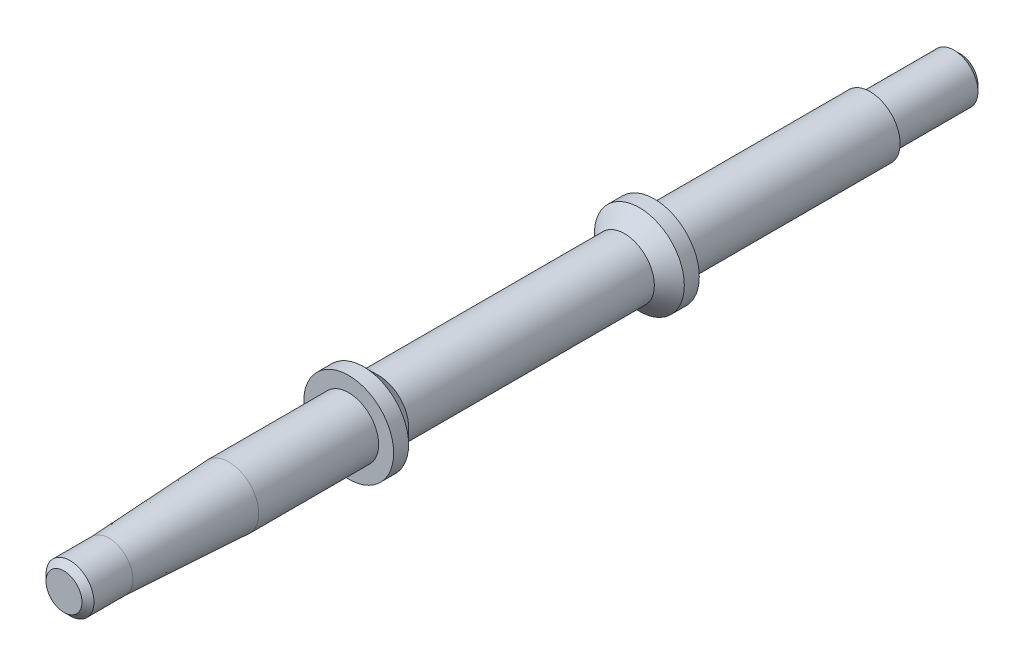
SolidWorks part; units mm, degrees
material "Ст20"
ref_plane "Front Plane" through (0, 0, 0) normal (0, 0, 1) x (1, 0, 0)
ref_plane "Top Plane" through (0, 0, 0) normal (0, 1, 0) x (1, 0, 0)
ref_plane "Right Plane" through (0, 0, 0) normal (1, 0, 0) x (0, 0, -1)
sketch "Эскиз1" plane through (0, 0, 0) normal (0, 0, 1) x (1, 0, 0)
  circle A0 centre (0, 0) radius 7.5
extrude "Бобышка-Вытянуть1" add sketch "Эскиз1" against normal blind 51
sketch "Эскиз2" plane through (0, 0, 0) normal (0, 0, 1) x (1, 0, 0)
  circle A0 centre (0, 0) radius 5
extrude "Бобышка-Вытянуть2" add sketch "Эскиз2" along normal blind 20
sketch "Эскиз3" plane through (0, 0, -51) normal (0, 0, -1) x (-1, 0, 0)
  circle A0 centre (0, 0) radius 5
extrude "Бобышка-Вытянуть3" add sketch "Эскиз3" along normal blind 36
cosmetic thread "Условное изображение резьбы1" parameters "D1"=19, "D2"=8.344
ref_plane "Плоскость1" through (0, 0, -2.5) normal (0, 0, 1) x (1, 0, 0)
sketch "Эскиз4" plane through (0, 0, -2.5) normal (0, 0, 1) x (1, 0, 0)
  circle A0 centre (0, 0) radius 5
extrude "Вырез-Вытянуть1" cut sketch "Эскиз4" against normal blind 46 flip side to cut
sketch "Эскиз5" plane through (0, 0, -87) normal (0, 0, -1) x (-1, 0, 0)
  circle A0 centre (0, 0) radius 4
extrude "Бобышка-Вытянуть4" add sketch "Эскиз5" along normal blind 15
sketch "Эскиз6" plane through (0, 0, 20) normal (0, 0, 1) x (1, 0, 0)
  circle A0 centre (0, 0) radius 5
extrude "Бобышка-Вытянуть5" add sketch "Эскиз6" along normal blind 20 draft 2.863
sketch "Эскиз7" plane through (0, 0, 40) normal (0, 0, 1) x (1, 0, 0)
  circle A0 centre (0, 0) radius 4
extrude "Бобышка-Вытянуть6" add sketch "Эскиз7" along normal blind 7.5
cosmetic thread "Условное изображение резьбы2" parameters "D1"=7.5, "D2"=6.891
chamfer "Фаска1" distance 2.5 angle 45 2 edges at (5, 0, -2.5) (5, 0, -48.5)
chamfer "Фаска2" distance 1 angle 45 2 edges at (-4, 0, -102) (4, 0, 47.5)
